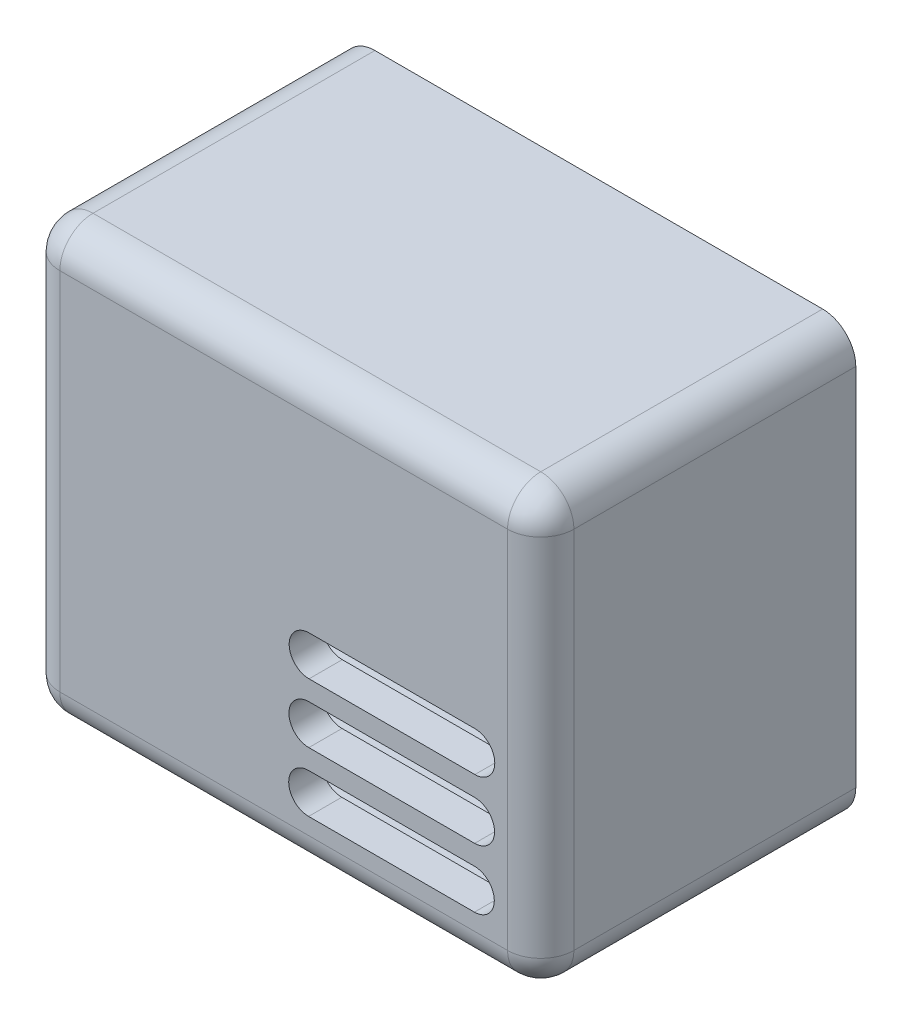
SolidWorks part; units mm, degrees
ref_plane "Plan de face" through (0, 0, 0) normal (0, 0, 1) x (1, 0, 0)
ref_plane "Plan de dessus" through (0, 0, 0) normal (0, 1, 0) x (1, 0, 0)
ref_plane "Plan de droite" through (0, 0, 0) normal (1, 0, 0) x (0, 0, -1)
sketch "Esquisse1" plane through (0, 0, 0) normal (0, 0, 1) x (1, 0, 0)
  line L0 (5.75, -4.4) -> (0.75, -4.4) construction
  line L1 (7.75, -6.5) -> (-7.75, -6.5)
  line L2 (7.75, -6.5) -> (7.75, 6.5)
  line L3 (7.75, 6.5) -> (-7.75, 6.5)
  line L4 (-7.75, -6.5) -> (-7.75, 6.5)
  line L5 (7.75, -6.5) -> (-7.75, 6.5) construction
  line L6 (7.75, 6.5) -> (-7.75, -6.5) construction
  line L7 (5.75, -5) -> (0.75, -5)
  line L8 (5.75, -3.8) -> (0.75, -3.8)
  line L9 (5.7571, -2.6) -> (0.7571, -2.6) construction
  line L12 (5.7571, -3.2) -> (0.7571, -3.2)
  line L15 (3.25, -4.4) -> (3.2743, 1.7959) construction
  line L16 (5.7571, -2) -> (0.7571, -2)
  line L17 (5.7641, -0.8) -> (0.7641, -0.8) construction
  line L18 (5.7641, -1.4) -> (0.7641, -1.4)
  line L19 (5.7641, -0.2) -> (0.7641, -0.2)
  arc A0 (5.75, -5) -> (5.75, -3.8) centre (5.75, -4.4) ccw
  arc A1 (0.75, -3.8) -> (0.75, -5) centre (0.75, -4.4) ccw
  arc A6 (5.7571, -3.2) -> (5.7571, -2) centre (5.7571, -2.6) ccw
  arc A7 (0.7571, -2) -> (0.7571, -3.2) centre (0.7571, -2.6) ccw
  arc A8 (5.7641, -1.4) -> (5.7641, -0.2) centre (5.7641, -0.8) ccw
  arc A9 (0.7641, -0.2) -> (0.7641, -1.4) centre (0.7641, -0.8) ccw
  point P0 (0, 0)
  point P8 (3.25, -4.4)
  point P16 (3.2571, -2.6)
  point P23 (3.2641, -0.8)
  dimension "D6" = 0.6
  dimension "D1" = 13
  dimension "D2" = 15.5
  dimension "D3" = 2
  dimension "D4" = 5
  dimension "D5" = 1.5
  dimension "D7" = 3
extrude "Boss.-Extru.1" add sketch "Esquisse1" along normal blind 1
sketch "Esquisse2" plane through (0, 0, 0) normal (0, 0, -1) x (-1, 0, 0)
  line L1 (-7.75, -6.5) -> (7.75, -6.5)
  line L2 (-7.75, -6.5) -> (-7.75, 6.5)
  line L3 (-7.75, 6.5) -> (7.75, 6.5)
  line L4 (7.75, -6.5) -> (7.75, 6.5)
  line L5 (6.75, 5.5) -> (-6.75, 5.5)
  line L6 (6.75, 5.5) -> (6.75, -5.5)
  line L7 (6.75, -5.5) -> (-6.75, -5.5)
  line L8 (-6.75, 5.5) -> (-6.75, -5.5)
  line L9 (6.75, 5.5) -> (-6.75, -5.5) construction
  line L10 (6.75, -5.5) -> (-6.75, 5.5) construction
  point P6 (0, 0)
  dimension "D1" = 1
  dimension "D2" = 1
  dimension "D3" = 1
  dimension "D4" = 1
extrude "Boss.-Extru.2" add sketch "Esquisse2" along normal blind 8.5
sketch "Esquisse3" plane through (-7.75, 0, 0) normal (-1, 0, 0) x (0, 0, 1)
  line L0 (-8.5, -6.5) -> (-8.5, 6.5) construction
  line L1 (-8.5, 5.4041) -> (-5.5, 5.4041)
  line L2 (-8.5, 5.4041) -> (-8.5, -4.5959)
  line L3 (-8.5, -4.5959) -> (-5.5, -4.5959)
  line L4 (-5.5, 5.4041) -> (-5.5, -4.5959)
  line L5 (-8.5, 0.4041) -> (-2.7983, 0.4041) construction
  point P8 (-5.5, 0.4041)
  dimension "D1" = 10
  dimension "D2" = 3
extrude "Enlèv. mat.-Extru.1" cut sketch "Esquisse3" against normal up to next
sketch "Esquisse4" plane through (0, 0, 0) normal (0, 0, -1) x (-1, 0, 0)
  line L0 (-6.75, 5.5) -> (-6.75, -5.5) construction
  line L1 (6.75, 5.5) -> (-6.75, 5.5) construction
  circle A0 centre (-4.15, 2.9) radius 2.25
  dimension "D1" = 4.5
  dimension "D2" = 2.6
  dimension "D3" = 2.6
extrude "Boss.-Extru.3" add sketch "Esquisse4" along normal blind 1.4
sketch "Esquisse5" plane through (0, 0, -1.4) normal (0, 0, -1) x (-1, 0, 0)
  circle A0 centre (-4.15, 2.9) radius 1.5
  circle A1 centre (-4.15, 2.9) radius 0.9
  dimension "D1" = 3
  dimension "D2" = 1.8
extrude "Boss.-Extru.4" add sketch "Esquisse5" along normal blind 4
fillet "Congé1" radius 1.5 1 edges at (6.4, 2.9, 0)
fillet "Congé2" radius 1 8 edges at (-7.75, 6.5, -3.75) (-7.75, -6.5, -3.75) (7.75, 6.5, -3.75) (7.75, -6.5, -3.75) (0, 6.5, 1) (7.75, 0, 1) (0, -6.5, 1) (-7.75, 0, 1)
